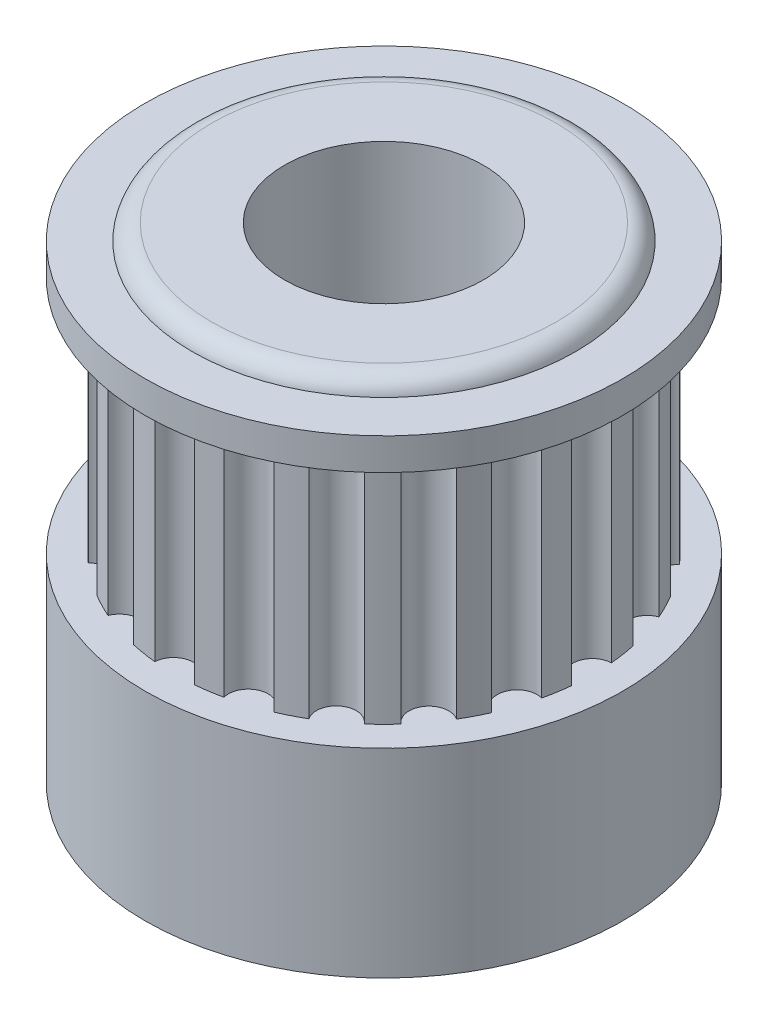
SolidWorks part; units mm, degrees
ref_plane "Front Plane" through (0, 0, 0) normal (0, 0, 1) x (1, 0, 0)
ref_plane "Top Plane" through (0, 0, 0) normal (0, 1, 0) x (1, 0, 0)
ref_plane "Right Plane" through (0, 0, 0) normal (1, 0, 0) x (0, 0, -1)
sketch "Sketch1" plane through (0, 0, 0) normal (0, 1, 0) x (1, 0, 0)
  circle A0 centre (0, 0) radius 6
  dimension "D1" = 12
extrude "Boss-Extrude1" add sketch "Sketch1" along normal blind 5
sketch "Sketch2" plane through (0, 5, 0) normal (0, 1, 0) x (1, 0, 0)
  circle A0 centre (0, 0) radius 5.2625
extrude "Boss-Extrude2" add sketch "Sketch2" along normal blind 6
sketch "Sketch3" plane through (0, 11, 0) normal (0, 1, 0) x (1, 0, 0)
  circle A0 centre (-1.6039, 5.0121) radius 0.5
  circle A1 centre (0, 0) radius 5.2625 construction
  circle A2 centre (0.0235, 5.2624) radius 0.5
  circle A3 centre (1.6485, 4.9976) radius 0.5
  circle A4 centre (3.1122, 4.2436) radius 0.5
  circle A5 centre (4.2712, 3.0742) radius 0.5
  circle A6 centre (5.0121, 1.6039) radius 0.5
  circle A7 centre (5.2624, -0.0235) radius 0.5
  circle A8 centre (4.9976, -1.6485) radius 0.5
  circle A9 centre (4.2436, -3.1122) radius 0.5
  circle A10 centre (3.0742, -4.2712) radius 0.5
  circle A11 centre (1.6039, -5.0121) radius 0.5
  circle A12 centre (-0.0235, -5.2624) radius 0.5
  circle A13 centre (-1.6485, -4.9976) radius 0.5
  circle A14 centre (-3.1122, -4.2436) radius 0.5
  circle A15 centre (-4.2712, -3.0742) radius 0.5
  circle A16 centre (-5.0121, -1.6039) radius 0.5
  circle A17 centre (-5.2624, 0.0235) radius 0.5
  circle A18 centre (-4.9976, 1.6485) radius 0.5
  circle A19 centre (-4.2436, 3.1122) radius 0.5
  circle A20 centre (-3.0742, 4.2712) radius 0.5
  dimension "D1" = 1
  dimension "D2" = 20
extrude "Cut-Extrude1" cut sketch "Sketch3" against normal blind 6
sketch "Sketch4" plane through (0, 11, 0) normal (0, 1, 0) x (1, 0, 0)
  circle A0 centre (0, 0) radius 6
extrude "Boss-Extrude3" add sketch "Sketch4" along normal blind 0.8
sketch "Sketch5" plane through (0, 11.8, 0) normal (0, 1, 0) x (1, 0, 0)
  circle A0 centre (0, 0) radius 4.8195
extrude "Boss-Extrude4" add sketch "Sketch5" along normal blind 0.4
fillet "Fillet3" radius 0.5 1 edges at (0, 12.2, 4.8195)
sketch "Sketch6" plane through (0, 12.2, 0) normal (0, 1, 0) x (1, 0, 0)
  circle A0 centre (0, 0) radius 2.5
  dimension "D1" = 5
extrude "Cut-Extrude2" cut sketch "Sketch6" against normal through all
